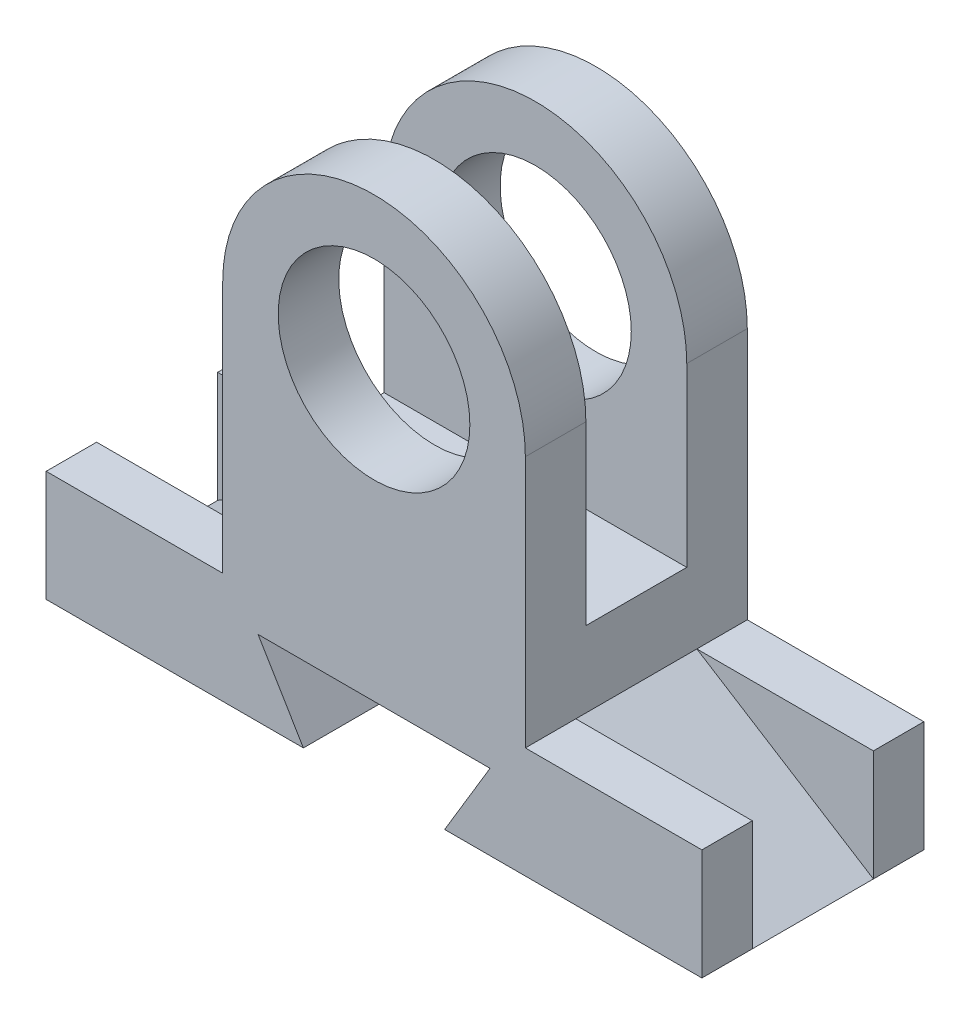
SolidWorks part; units mm, degrees
ref_plane "Front Plane" through (0, 0, 0) normal (0, 0, 1) x (1, 0, 0)
ref_plane "Top Plane" through (0, 0, 0) normal (0, 1, 0) x (1, 0, 0)
ref_plane "Right Plane" through (0, 0, 0) normal (1, 0, 0) x (0, 0, -1)
sketch "Sketch1" plane through (0, 0, 0) normal (0, 0, 1) x (1, 0, 0)
  line L0 (-65, -11) -> (-14, -11)
  line L1 (-65, -11) -> (-65, 11)
  line L2 (65, -11) -> (65, 11)
  line L3 (-65, 11) -> (65, 11)
  line L4 (-65, -11) -> (65, 11) construction
  line L5 (65, -11) -> (-65, 11) construction
  line L6 (-23, 4) -> (23, 4)
  line L8 (-23, 4) -> (-14, -11)
  line L9 (23, 4) -> (14, -11)
  line L10 (14, -11) -> (65, -11)
  line L11 (30, 11) -> (65, -11)
  line L13 (-30, 61) -> (-30, 11)
  line L14 (-30, 11) -> (30, 11)
  line L15 (30, 61) -> (30, 11)
  line L16 (-65, -11) -> (-30, 11)
  arc A0 (30, 61) -> (-30, 61) centre (0, 61) ccw
  circle A1 centre (0, 61) radius 19
  point P1 (0, 0)
  point P3 (0, 4)
  point P12 (0, -11)
  point P16 (0, 11)
  point P17 (0, 11)
  dimension "D6" = 38
  dimension "D1" = 22
  dimension "D2" = 130
  dimension "D3" = 46
  dimension "D4" = 28
  dimension "D5" = 15
  dimension "D7" = 60
extrude "Boss-Extrude1" add sketch "Sketch1" along normal blind 22 and the other way blind 22 contours L16 L0 L8 L6 L9 L10 L11 L3 | L3 L11 L2 | L1 L16 L3 region at (-46.7983, -1.1163, 0) region at (-53.3333, 3.6667, 0) region at (53.3333, 3.6667, 0)
extrude "Cut-Extrude1" cut sketch "Sketch1<3>" against normal blind 12 and the other way blind 12 contours L1 L16 L3 | L3 L11 L2 region at (-53.3333, 3.6667, 0) region at (53.3333, 3.6667, 0)
sketch "Sketch1<3>" plane through (0, 0, 0) normal (0, 0, 1) x (1, 0, 0) same geometry as "Sketch1"
extrude "Boss-Extrude2" add sketch "Sketch1<4>" along normal blind 22 and the other way blind 22 contours L15 A0 L13 L3 A1 region at (-29, 36, 0)
sketch "Sketch1<4>" plane through (0, 0, 0) normal (0, 0, 1) x (1, 0, 0) same geometry as "Sketch1"
sketch "Sketch2" plane through (30, 0, 0) normal (1, 0, 0) x (0, 0, -1)
  line L0 (22, 61) -> (-22, 61) construction
  line L1 (-10, 97.3196) -> (10, 97.3196)
  line L2 (-10, 97.3196) -> (-10, 26)
  line L3 (-10, 26) -> (10, 26)
  line L4 (10, 97.3196) -> (10, 26)
  point P6 (0, 61)
  point P7 (0, 97.3196)
  point P8 (10, 97.3196)
  dimension "D1" = 20
  dimension "D2" = 37
extrude "Cut-Extrude2" cut sketch "Sketch2" against normal through all
